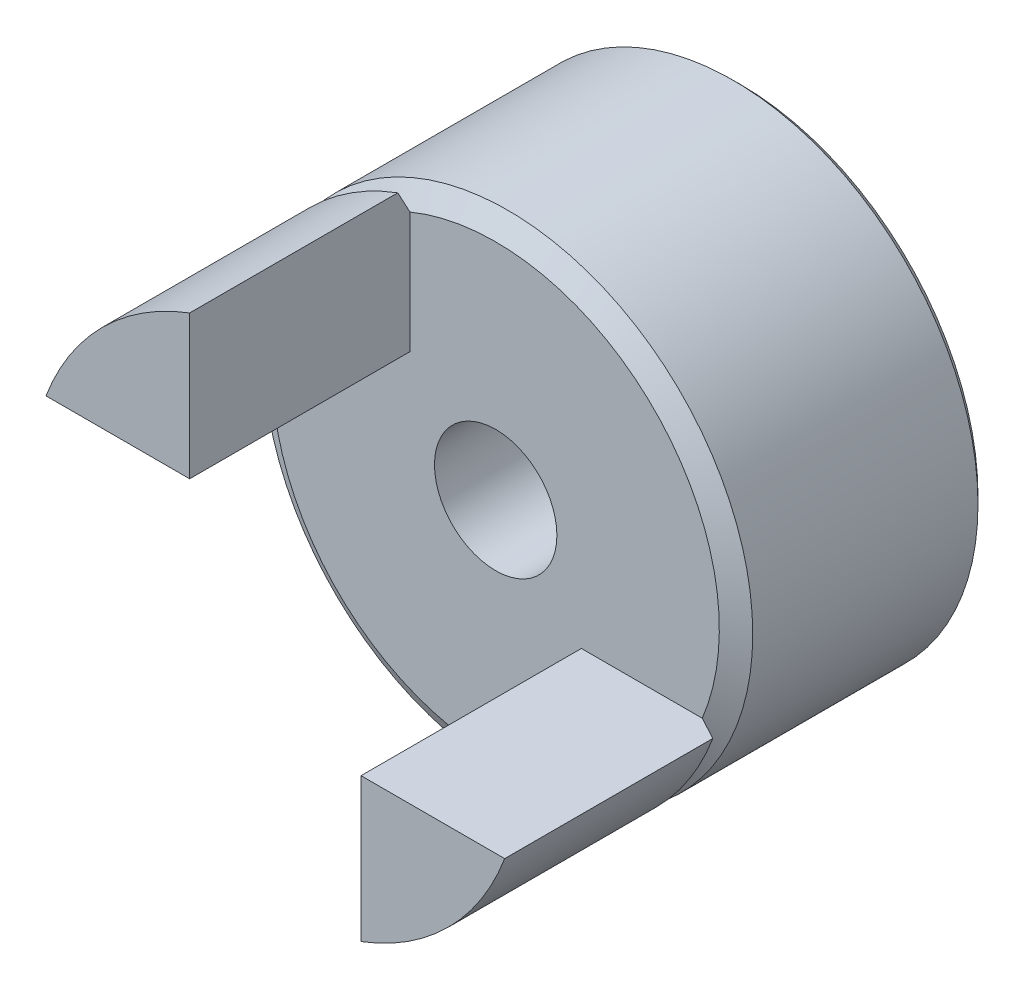
SolidWorks part; units mm, degrees
ref_plane "정면" through (0, 0, 0) normal (0, 0, 1) x (1, 0, 0)
ref_plane "윗면" through (0, 0, 0) normal (0, 1, 0) x (1, 0, 0)
ref_plane "우측면" through (0, 0, 0) normal (1, 0, 0) x (0, 0, -1)
sketch "스케치1" plane through (0, 0, 0) normal (0, 0, 1) x (1, 0, 0)
  circle A0 centre (0, 0) radius 10
  circle A1 centre (0, 0) radius 2.5
  dimension "D1" = 5
  dimension "D2" = 20
extrude "보스-돌출1" add sketch "스케치1" along normal blind 10
chamfer "모따기1" distance 0.3 angle 45 2 edges at (2.5, 0, 0) (10, 0, 0)
sketch "스케치2" plane through (0, 0, 10) normal (0, 0, 1) x (1, 0, 0)
  line L1 (-10, -3.5) -> (10, -3.5)
  line L2 (-10, -3.5) -> (-10, 3.5)
  line L3 (-10, 3.5) -> (10, 3.5)
  line L4 (10, -3.5) -> (10, 3.5)
  line L5 (-10, -3.5) -> (10, 3.5) construction
  line L6 (-10, 3.5) -> (10, -3.5) construction
  line L7 (-3.5, -10) -> (3.5, -10)
  line L8 (-3.5, -10) -> (-3.5, 10)
  line L9 (-3.5, 10) -> (3.5, 10)
  line L10 (3.5, -10) -> (3.5, 10)
  line L11 (-3.5, -10) -> (3.5, 10) construction
  line L12 (-3.5, 10) -> (3.5, -10) construction
  circle A1 centre (0, 0) radius 10
  circle A2 centre (0, 0) radius 10
  circle M5 centre (0, 0) radius 10
  dimension "D2" = 7
  dimension "D1" = 0
extrude "보스-돌출2" add sketch "스케치2" along normal blind 9 contours L3 L8 M5 | L10 L1 M5 region at (-5.735, 5.735, 10) region at (5.735, -5.735, 10)
sketch "스케치3" plane through (0, 0, 0) normal (0, 1, 0) x (1, 0, 0)
  line L1 (9.134, -10) -> (10, -10.5)
  line L2 (10, -10.5) -> (10, -9.5)
  line L3 (10, -9.5) -> (9.134, -10)
  line L7 (0, 0) -> (0, -17.4659) construction
  circle A0 centre (9.7113, -10) radius 0.2887 construction
  dimension "D1" = 10
  dimension "D2" = 1
  dimension "D3" = 9.5
revolve "컷-회전1" cut sketch "스케치3" angle 360 about L7
